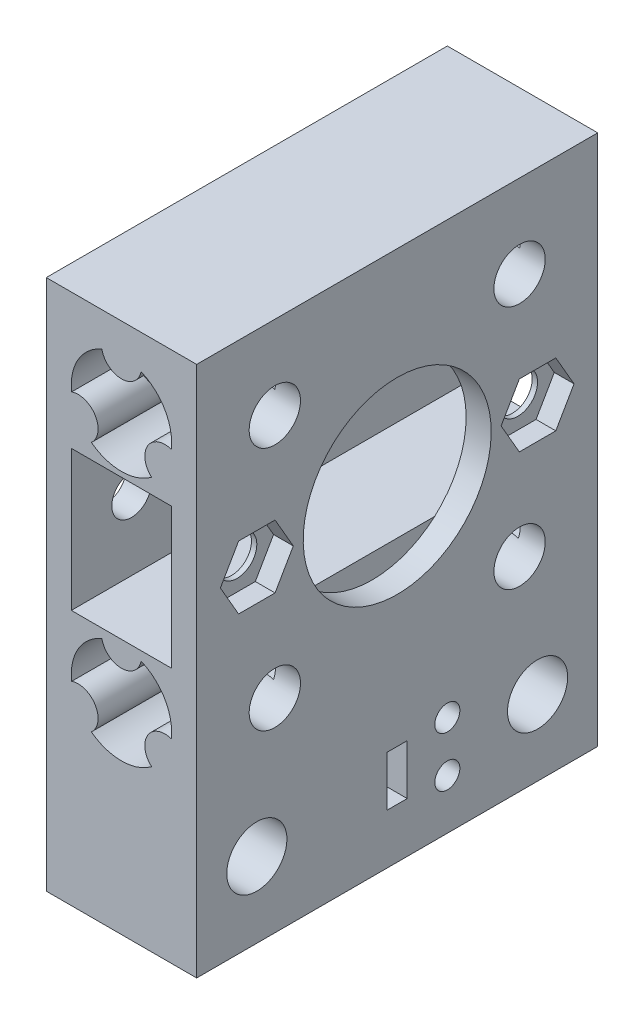
SolidWorks part; units mm, degrees
ref_plane "Front Plane" through (0, 0, 0) normal (0, 0, 1) x (1, 0, 0)
ref_plane "Top Plane" through (0, 0, 0) normal (0, 1, 0) x (1, 0, 0)
ref_plane "Right Plane" through (0, 0, 0) normal (1, 0, 0) x (0, 0, -1)
sketch "Sketch1" plane through (0, 0, 0) normal (0, 0, 1) x (1, 0, 0)
  line L0 (0, 15.875) -> (0, -15.875) construction
  line L1 (9.525, 28.575) -> (-9.525, 28.575)
  line L2 (9.525, 28.575) -> (9.525, -28.575)
  line L3 (9.525, -28.575) -> (-9.525, -28.575)
  line L4 (-9.525, 28.575) -> (-9.525, -28.575)
  line L5 (9.525, 28.575) -> (-9.525, -28.575) construction
  line L6 (9.525, -28.575) -> (-9.525, 28.575) construction
  circle A0 centre (0, 15.875) radius 3.81
  circle A1 centre (0, -15.875) radius 3.81
  circle A2 centre (0, -15.875) radius 6.35
  circle A3 centre (0, 15.875) radius 6.35
  circle A4 centre (0, -9.525) radius 2.54
  circle A5 centre (5.4993, -19.05) radius 2.54
  circle A6 centre (-5.4993, -19.05) radius 2.54
  circle A7 centre (0, 22.225) radius 2.54
  circle A8 centre (5.4993, 12.7) radius 2.54
  circle A9 centre (-5.4993, 12.7) radius 2.54
  point P0 (0, 0)
  point P9 (0, 0)
  point P15 (3.2996, -17.78)
  point P17 (3.815, -20.9513)
  point P22 (6.3037, -16.6407)
  dimension "D4" = 7.62
  dimension "D5" = 7.62
  dimension "D6" = 12.7
  dimension "D7" = 12.7
  dimension "D9" = 3
  dimension "D1" = 57.15
  dimension "D2" = 19.05
  dimension "D3" = 31.75
  dimension "D8" = 3
extrude "Boss-Extrude1" add sketch "Sketch1" along normal blind 50.8 contours L2 L1 L4 L3
extrude "Cut-Extrude1" cut sketch "Sketch1<4>" along normal through all contours A2
sketch "Sketch1<4>" plane through (0, 0, 0) normal (0, 0, 1) x (1, 0, 0) same geometry as "Sketch1"
extrude "Boss-Extrude2" add sketch "Sketch1<5>" along normal through all contours A4 | A6 | A5
sketch "Sketch1<5>" plane through (0, 0, 0) normal (0, 0, 1) x (1, 0, 0) same geometry as "Sketch1"
extrude "Cut-Extrude2" cut sketch "Sketch1<6>" along normal through all contours A3
sketch "Sketch1<6>" plane through (0, 0, 0) normal (0, 0, 1) x (1, 0, 0) same geometry as "Sketch1"
extrude "Boss-Extrude3" add sketch "Sketch1<7>" along normal through all contours A9 | A7 | A8
sketch "Sketch1<7>" plane through (0, 0, 0) normal (0, 0, 1) x (1, 0, 0) same geometry as "Sketch1"
sketch "Sketch4" plane through (-9.525, 0, 0) normal (-1, 0, 0) x (0, 0, 1)
  line L0 (0, 28.575) -> (50.8, -28.575) construction
  line L1 (50.8, 28.575) -> (0, -28.575) construction
  line L3 (40.9, -15.5) -> (9.9, -15.5) construction
  line L4 (40.9, -15.5) -> (40.9, 15.5) construction
  line L5 (40.9, 15.5) -> (9.9, 15.5) construction
  line L6 (9.9, -15.5) -> (9.9, 15.5) construction
  line L7 (40.9, -15.5) -> (9.9, 15.5) construction
  line L8 (40.9, 15.5) -> (9.9, -15.5) construction
  circle A0 centre (25.4, 0) radius 11
  circle A1 centre (25.4, 0) radius 8.5
  circle A2 centre (9.9, 15.5) radius 1.7
  circle A3 centre (40.9, 15.5) radius 1.7
  circle A4 centre (40.9, -15.5) radius 1.7
  circle A5 centre (9.9, -15.5) radius 1.7
  dimension "D1" = 22
  dimension "D2" = 17
  dimension "D5" = 3.4
  dimension "D6" = 3.4
  dimension "D7" = 3.4
  dimension "D8" = 3.4
  dimension "D3" = 31
  dimension "D4" = 31
extrude "Cut-Extrude3" cut sketch "Sketch4" against normal through all contours A1
extrude "Cut-Extrude4" cut sketch "Sketch4<3>" against normal blind 2.5 contours A0
sketch "Sketch4<3>" plane through (-9.525, 0, 0) normal (-1, 0, 0) x (0, 0, 1) same geometry as "Sketch4"
sketch "Sketch5" plane through (0, 0, 0) normal (0, 0, -1) x (-1, 0, 0)
  line L1 (6.35, 8.89) -> (-6.35, 8.89)
  line L2 (6.35, 8.89) -> (6.35, -8.89)
  line L3 (6.35, -8.89) -> (-6.35, -8.89)
  line L4 (-6.35, 8.89) -> (-6.35, -8.89)
  line L5 (6.35, 8.89) -> (-6.35, -8.89) construction
  line L6 (6.35, -8.89) -> (-6.35, 8.89) construction
  point P0 (0, 0)
  dimension "D1" = 12.7
  dimension "D2" = 17.78
extrude "Cut-Extrude5" cut sketch "Sketch5" against normal through all
extrude "Cut-Extrude6" cut sketch "Sketch4<4>" against normal through all contours A2 | A5 | A4 | A3
sketch "Sketch4<4>" plane through (-9.525, 0, 0) normal (-1, 0, 0) x (0, 0, 1) same geometry as "Sketch4"
sketch "Sketch6" plane through (9.525, 0, 0) normal (1, 0, 0) x (0, 0, -1)
  circle A0 centre (-40.9, 15.5) radius 3.25
  circle A1 centre (-9.9, 15.5) radius 3.25
  circle A2 centre (-9.9, -15.5) radius 3.25
  circle A3 centre (-40.9, -15.5) radius 3.25
  dimension "D1" = 6.5
  dimension "D2" = 6.5
  dimension "D3" = 6.5
  dimension "D4" = 6.5
extrude "Cut-Extrude7" cut sketch "Sketch6" against normal blind 17.78 contours A3 | A2 | A1 | A0
sketch "Sketch7" plane through (9.525, 0, 0) normal (1, 0, 0) x (0, 0, -1)
  line L0 (-25.4, 0) -> (-7.62, 0)
  line L1 (-25.4, 0) -> (-43.18, 0)
  line L3 (-47.7988, 0) -> (-45.4894, -4)
  line L4 (-45.4894, -4) -> (-40.8706, -4)
  line L5 (-40.8706, -4) -> (-38.5612, 0)
  line L6 (-38.5612, 0) -> (-40.8706, 4)
  line L7 (-40.8706, 4) -> (-45.4894, 4)
  line L8 (-45.4894, 4) -> (-47.7988, 0)
  line L9 (-12.2388, 0) -> (-9.9294, -4)
  line L10 (-9.9294, -4) -> (-5.3106, -4)
  line L11 (-5.3106, -4) -> (-3.0012, 0)
  line L12 (-3.0012, 0) -> (-5.3106, 4)
  line L13 (-5.3106, 4) -> (-9.9294, 4)
  line L14 (-9.9294, 4) -> (-12.2388, 0)
  circle A0 centre (-43.18, 0) radius 4 construction
  circle A2 centre (-7.62, 0) radius 4 construction
  dimension "D4" = 8
  dimension "D1" = 17.78
  dimension "D2" = 17.78
  dimension "D3" = 8
extrude "Cut-Extrude8" cut sketch "Sketch7" against normal blind 2.5 contours L7 L8 L3 L4 L5 L6
extrude "Cut-Extrude9" cut sketch "Sketch7<3>" against normal blind 2.5 contours L12 L13 L14 L9 L10 L11
sketch "Sketch7<3>" plane through (9.525, 0, 0) normal (1, 0, 0) x (0, 0, -1) same geometry as "Sketch7"
sketch "Sketch9" plane through (7.025, 0, 0) normal (1, 0, 0) x (0, 0, -1)
  line L2 (-12.2388, 0) -> (-3.0012, 0) construction
  line L6 (-47.7988, 0) -> (-38.5612, 0) construction
  circle A0 centre (-43.18, 0) radius 2.5
  circle A1 centre (-7.62, 0) radius 2.5
  dimension "D1" = 5
  dimension "D2" = 5
extrude "Cut-Extrude10" cut sketch "Sketch9" against normal through all contours A1 | A0
sketch "Sketch10" plane through (9.525, 0, 0) normal (1, 0, 0) x (0, 0, -1)
  circle A0 centre (-25.4, 0) radius 11.9062
  dimension "D1" = 23.8125
extrude "Cut-Extrude11" cut sketch "Sketch10" against normal up to surface (3.175 mm away) up to face at (6.35, 2.5, 7.62)
sketch "Sketch11" plane through (0, 28.575, 0) normal (0, 1, 0) x (1, 0, 0)
  line L1 (-9.525, 0) -> (9.525, 0)
  line L2 (-9.525, 0) -> (-9.525, -50.8)
  line L3 (-9.525, -50.8) -> (9.525, -50.8)
  line L4 (9.525, 0) -> (9.525, -50.8)
extrude "Cut-Extrude12" cut sketch "Sketch11" against normal blind 2.54
sketch "Sketch12" plane through (0, -28.575, 0) normal (0, -1, 0) x (1, 0, 0)
  line L1 (-9.525, 50.8) -> (9.525, 50.8)
  line L2 (-9.525, 50.8) -> (-9.525, 0)
  line L3 (-9.525, 0) -> (9.525, 0)
  line L4 (9.525, 50.8) -> (9.525, 0)
extrude "Boss-Extrude4" add sketch "Sketch12" along normal blind 12.7
sketch "Sketch13" plane through (9.525, 0, 0) normal (1, 0, 0) x (0, 0, -1)
  line L0 (-50.8, -41.275) -> (-50.8, -31.75) construction
  line L1 (-50.8, 26.035) -> (-50.8, -41.275) construction
  line L2 (-50.8, -31.75) -> (0, -31.75) construction
  line L3 (0, 26.035) -> (0, -41.275) construction
  line L4 (0, -31.75) -> (-7.62, -31.75)
  line L5 (-50.8, -41.275) -> (-50.8, -31.75)
  line L6 (0, -31.75) -> (0, -41.275)
  line L7 (0, -33.5271) -> (0, -36.3229)
  line L8 (-50.8, -33.5271) -> (-50.8, -36.3229)
  line L9 (-24.13, -28.575) -> (-19.05, -28.575)
  line L10 (-24.13, -34.925) -> (-26.67, -34.925)
  line L11 (-24.13, -34.925) -> (-24.13, -28.575)
  line L12 (-24.13, -28.575) -> (-26.67, -28.575)
  line L13 (-26.67, -34.925) -> (-26.67, -28.575)
  line L14 (-24.13, -34.925) -> (-26.67, -28.575) construction
  line L15 (-24.13, -28.575) -> (-26.67, -34.925) construction
  line L16 (-24.13, -34.925) -> (-19.05, -34.925)
  circle A0 centre (-43.18, -31.75) radius 3.81
  circle A1 centre (-43.18, -31.75) radius 6.35
  circle A2 centre (-7.62, -31.75) radius 3.81
  circle A3 centre (-7.62, -31.75) radius 6.35
  circle A4 centre (-43.18, -25.4) radius 2.54
  circle A5 centre (-37.6807, -34.925) radius 2.54
  arc A6 (-50.8, -36.3229) -> (-50.8, -33.5271) centre (-48.6793, -34.925) ccw
  circle A7 centre (-7.62, -25.4) radius 2.54
  arc A8 (0, -33.5271) -> (0, -36.3229) centre (-2.1207, -34.925) ccw
  circle A9 centre (-13.1193, -34.925) radius 2.54
  circle A10 centre (-19.05, -28.575) radius 1.5875
  circle A11 centre (-19.05, -34.925) radius 1.5875
  point P25 (-25.4, -31.75)
  dimension "D2" = 7.62
  dimension "D4" = 12.7
  dimension "D6" = 7.62
  dimension "D7" = 12.7
  dimension "D13" = 3.175
  dimension "D15" = 3.175
  dimension "D1" = 9.525
  dimension "D3" = 7.62
  dimension "D5" = 7.62
  dimension "D10" = 6.35
  dimension "D11" = 2.54
  dimension "D12" = 5.08
  dimension "D14" = 5.08
  dimension "D8" = 3
  dimension "D9" = 3
extrude "Cut-Extrude15" cut sketch "Sketch13" against normal through all contours A2 | A0
extrude "Cut-Extrude16" cut sketch "Sketch13<6>" against normal through all contours L12 L13 L10 L11
sketch "Sketch13<6>" plane through (9.525, 0, 0) normal (1, 0, 0) x (0, 0, -1) same geometry as "Sketch13"
extrude "Cut-Extrude17" cut sketch "Sketch13<7>" against normal through all contours A11 | A10
sketch "Sketch13<7>" plane through (9.525, 0, 0) normal (1, 0, 0) x (0, 0, -1) same geometry as "Sketch13"
